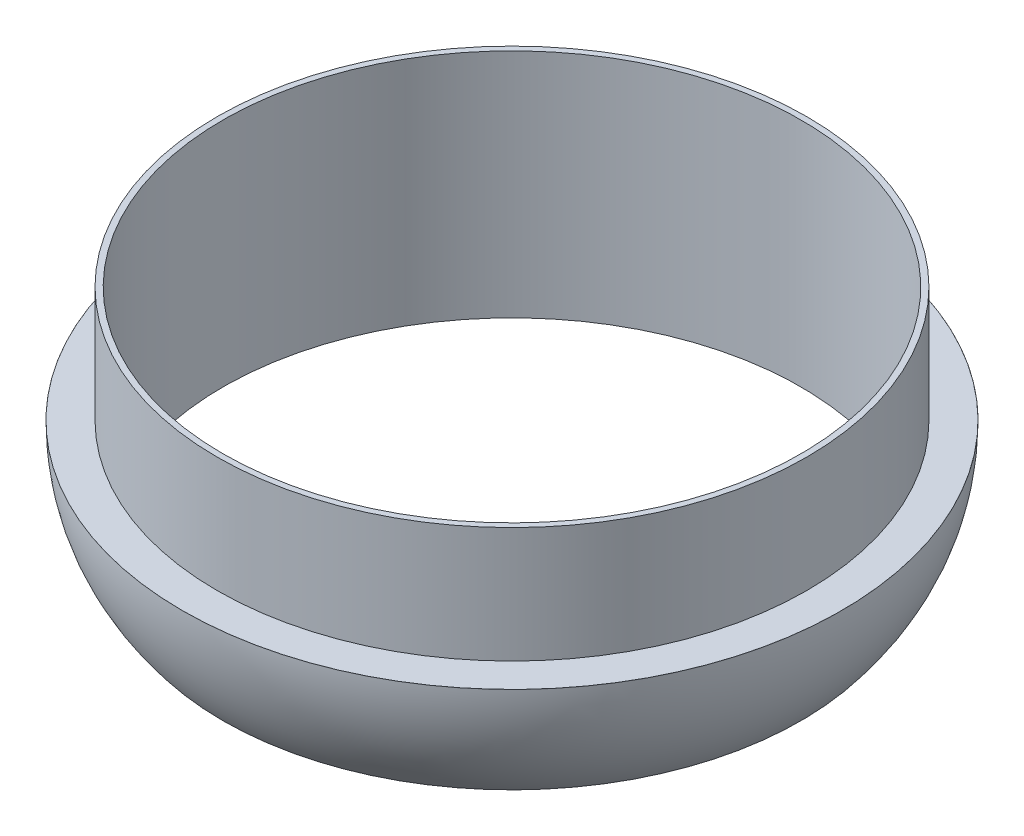
SolidWorks part; units mm, degrees
ref_plane "Front Plane" through (0, 0, 0) normal (0, 0, 1) x (1, 0, 0)
ref_plane "Top Plane" through (0, 0, 0) normal (0, 1, 0) x (1, 0, 0)
ref_plane "Right Plane" through (0, 0, 0) normal (1, 0, 0) x (0, 0, -1)
sketch "Sketch1" plane through (0, 0, 0) normal (0, 1, 0) x (1, 0, 0)
  circle A0 centre (0, 0) radius 28.5
  circle A1 centre (0, 0) radius 25.5
  circle A2 centre (0, 0) radius 25
  dimension "D1" = 57
  dimension "D2" = 51
  dimension "D3" = 50
extrude "Boss-Extrude2" add sketch "Sketch1" along normal blind 10 contours A1 A2 region at (-25.4279, 0, 0)
extrude "Boss-Extrude3" add sketch "Sketch1<4>" against normal blind 10 contours A0 A1 | A1 A2 region at (-27.6939, 0, 0) region at (-25.4279, 0, 0)
sketch "Sketch1<4>" plane through (0, 0, 0) normal (0, 1, 0) x (1, 0, 0) same geometry as "Sketch1"
sketch "Sketch3" plane through (0, 0, 0) normal (0, 0, 1) x (1, 0, 0)
fillet "Chamfer1" radius 3.5 1 edges at (0, -10, 28.5) type face fillet profile chamfer first side face at (0, -10, 28.5) second side face at (0, -10, 28.5)
fillet "Fillet1" radius 16 1 edges at (0, -6.5, 28.5)
